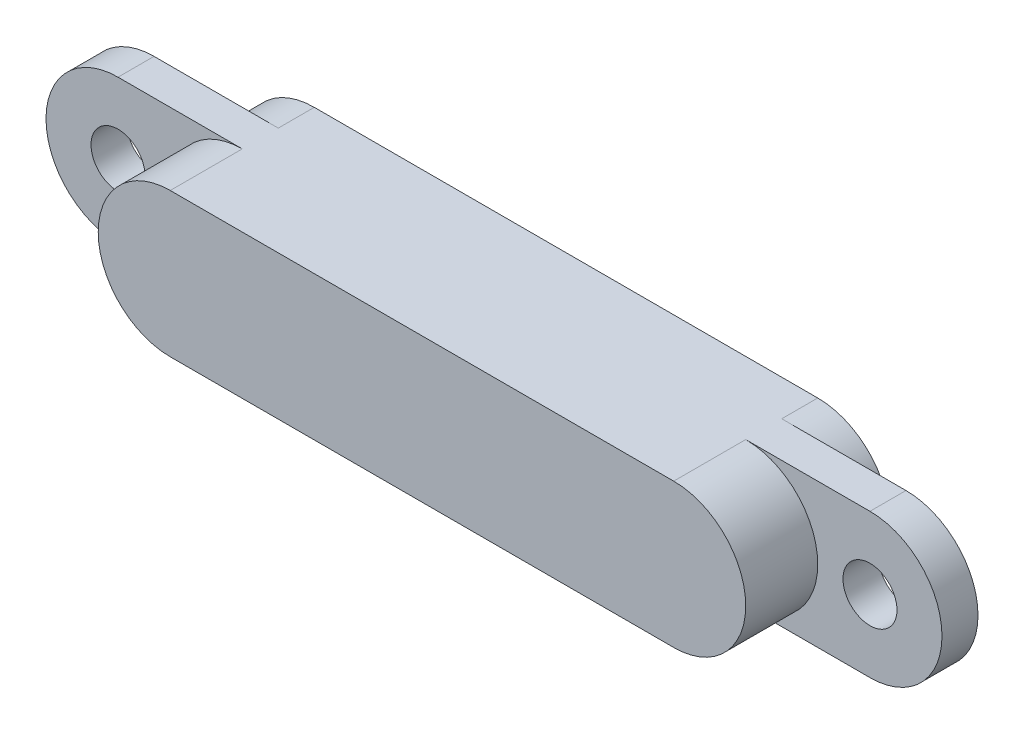
SolidWorks part; units mm, degrees
ref_plane "Front Plane" through (0, 0, 0) normal (0, 0, 1) x (1, 0, 0)
ref_plane "Top Plane" through (0, 0, 0) normal (0, 1, 0) x (1, 0, 0)
ref_plane "Right Plane" through (0, 0, 0) normal (1, 0, 0) x (0, 0, -1)
sketch "Sketch1" plane through (0, 0, 0) normal (0, 0, 1) x (1, 0, 0)
  line L0 (-10.44, 0) -> (10.44, 0) construction
  line L1 (-10.44, 2) -> (10.44, 2)
  line L2 (-10.44, -2) -> (10.44, -2)
  arc A0 (-10.44, 2) -> (-10.44, -2) centre (-10.44, 0) ccw
  arc A1 (10.44, -2) -> (10.44, 2) centre (10.44, 0) ccw
  point P3 (0, 0)
  dimension "D1" = 20.88
  dimension "D2" = 4
extrude "Boss-Extrude1" add sketch "Sketch1" along normal blind 4
sketch "Sketch2" plane through (0, 0, 4) normal (0, 0, 1) x (1, 0, 0)
  circle A0 centre (-10.44, 0) radius 0.75
  circle A1 centre (10.44, 0) radius 0.75
  dimension "D1" = 1.5
extrude "Cut-Extrude1" cut sketch "Sketch2" against normal blind 4
sketch "Sketch4" plane through (0, 0, 4) normal (0, 0, 1) x (1, 0, 0)
  line L0 (-6.99, 0) -> (6.99, 0) construction
  line L1 (-6.99, 2) -> (6.99, 2)
  line L2 (-6.99, -2) -> (6.99, -2)
  line L3 (10.44, 2) -> (-10.44, 2) construction
  arc A0 (-6.99, 2) -> (-6.99, -2) centre (-6.99, 0) ccw
  arc A1 (6.99, -2) -> (6.99, 2) centre (6.99, 0) ccw
  point P2 (0, 0)
  circle M5 centre (-10.44, 0) radius 0.75
  circle M6 centre (10.44, 0) radius 0.75
  arc M7 (-10.44, 2) -> (-10.44, -2) centre (-10.44, 0) ccw
  line M8 (-10.44, -2) -> (10.44, -2)
  arc M9 (10.44, -2) -> (10.44, 2) centre (10.44, 0) ccw
  line M10 (10.44, 2) -> (-10.44, 2)
  dimension "D1" = 17.98
extrude "Cut-Extrude2" cut sketch "Sketch4" against normal blind 2 contours A0 M10 M7 M8 M5 | A1 M8 M9 M10 M6 region at (-9.0576, 0, 4) region at (8.715, 1.9324, 4)
extrude "Cut-Extrude3" cut sketch "Sketch4<3>" against normal blind 1 from offset 3 contours A0 M10 M7 M8 M5 | A1 M8 M9 M10 M6 region at (-9.0576, 0, 4) region at (8.715, 1.9324, 4) offset against normal yes
sketch "Sketch4<3>" plane through (0, 0, 4) normal (0, 0, 1) x (1, 0, 0) same geometry as "Sketch4"
